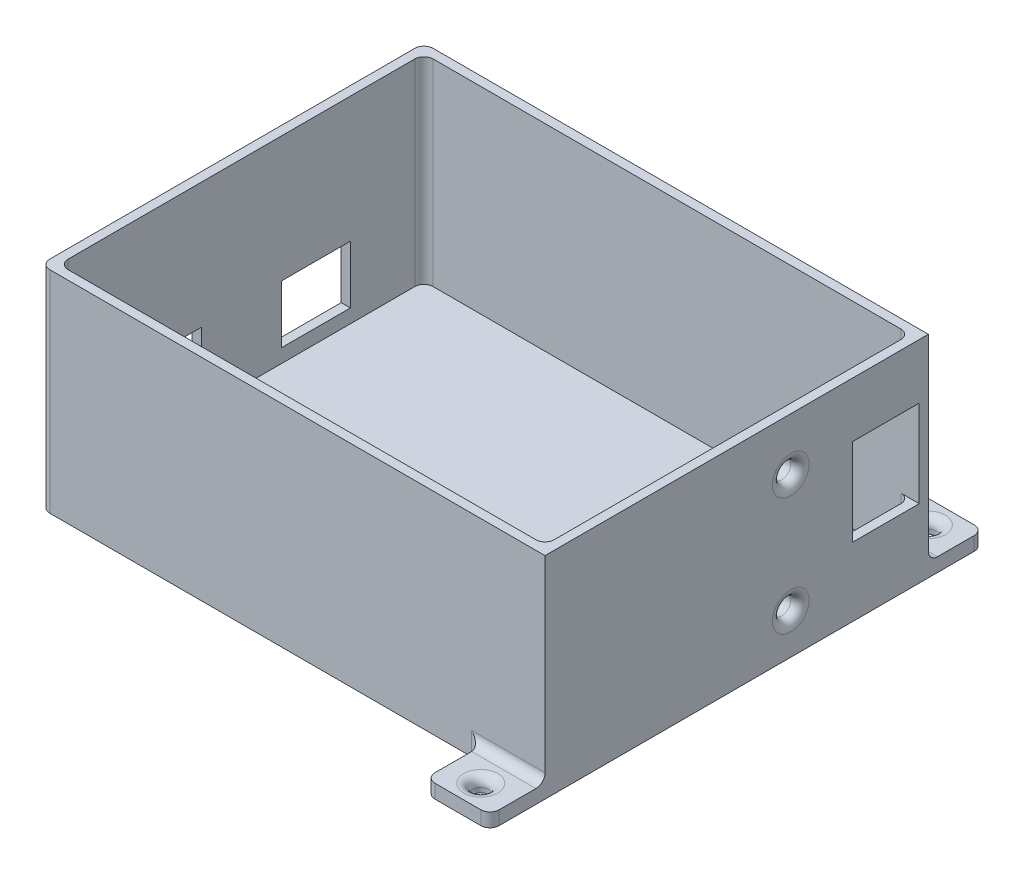
SolidWorks part; units mm, degrees
ref_plane "Front Plane" through (0, 0, 0) normal (0, 0, 1) x (1, 0, 0)
ref_plane "Top Plane" through (0, 0, 0) normal (0, 1, 0) x (1, 0, 0)
ref_plane "Right Plane" through (0, 0, 0) normal (1, 0, 0) x (0, 0, -1)
sketch "Sketch2" plane through (0, 0, 0) normal (0, 1, 0) x (1, 0, 0)
  line L1 (-16, 0) -> (-108, 0)
  line L2 (0, 0) -> (0, 83.6)
  line L3 (-16, 83.6) -> (-108, 83.6)
  line L4 (-110, 2) -> (-110, 81.6)
  line L5 (0, 0) -> (-16, 0)
  line L6 (0, 0) -> (0, -10)
  line L7 (-2, -12) -> (-12, -12)
  line L8 (-14, -2) -> (-14, -10)
  line L9 (0, 83.6) -> (-16, 83.6)
  line L10 (0, 83.6) -> (0, 93.6)
  line L11 (-2, 95.6) -> (-12, 95.6)
  line L12 (-14, 85.6) -> (-14, 93.6)
  arc A1 (-12, 95.6) -> (-14, 93.6) centre (-12, 93.6) ccw
  arc A2 (0, 93.6) -> (-2, 95.6) centre (-2, 93.6) ccw
  arc A3 (-16, 83.6) -> (-14, 85.6) centre (-16, 85.6) ccw
  arc A4 (-16, 0) -> (-14, -2) centre (-16, -2) cw
  arc A5 (-14, -10) -> (-12, -12) centre (-12, -10) ccw
  arc A6 (0, -10) -> (-2, -12) centre (-2, -10) cw
  arc A7 (-108, 0) -> (-110, 2) centre (-108, 2) cw
  arc A8 (-110, 81.6) -> (-108, 83.6) centre (-108, 81.6) cw
  dimension "D7" = 2
  dimension "D8" = 2
  dimension "D5" = 2
  dimension "D1" = 2
  dimension "D6" = 2
  dimension "D2" = 95.6
  dimension "D3" = 12
  dimension "D4" = 110
extrude "Boss-Extrude1" add sketch "Sketch2" along normal blind 46 contours A8 L4 A7 L1 L5 L2 L9 L3 region at (-54.9898, 0, -41.8)
extrude "Boss-Extrude2" add sketch "Sketch2<7>" along normal blind 3 contours A3 L9 L10 A2 L11 A1 L12 region at (-7.0382, 0, -89.5144)
sketch "Sketch2<7>" plane through (0, 0, 0) normal (0, 1, 0) x (1, 0, 0) same geometry as "Sketch2"
extrude "Boss-Extrude3" add sketch "Sketch2<8>" along normal blind 3 contours A6 L6 L5 A4 L8 A5 L7 region at (-7.0382, 0, 5.9144)
sketch "Sketch2<8>" plane through (0, 0, 0) normal (0, 1, 0) x (1, 0, 0) same geometry as "Sketch2"
fillet "Fillet1" radius 2 1 edges at (-8, 3, -83.6)
fillet "Fillet2" radius 2 1 edges at (-8, 3, 0)
sketch "Sketch3" plane through (0, 0, 0) normal (0, 1, 0) x (1, 0, 0)
  line L0 (-14, -2) -> (-14, -10) construction
  line L1 (-25.3, 0) -> (25.3, 0) construction
  line L2 (-14, 85.6) -> (-14, 93.6) construction
  line L4 (0, 83.6) -> (-108, 83.6) construction
  circle A0 centre (-7, -7) radius 1.7
  circle A1 centre (-7, 90.6) radius 1.7
  dimension "D1" = 7
  dimension "D3" = 7
  dimension "D2" = 7
  dimension "D4" = 7
extrude "Cut-Extrude5" cut sketch "Sketch3" along normal up to next
fillet "Fillet3" radius 2 2 edges at (-7, 3, 8.7) (-7, 3, -88.9)
sketch "Sketch4" plane through (0, 46, 0) normal (0, 1, 0) x (1, 0, 0)
  line L0 (0, 83.6) -> (-108, 83.6) construction
  line L1 (-106, 81.6) -> (-4, 81.6)
  line L2 (-108, 79.6) -> (-108, 4)
  line L3 (-106, 2) -> (-4, 2)
  line L4 (-2, 79.6) -> (-2, 4)
  line L5 (-110, 2) -> (-110, 81.6) construction
  line L6 (0, -25.3) -> (0, 25.3) construction
  line L7 (-25.3, 0) -> (25.3, 0) construction
  arc A0 (-2, 79.6) -> (-4, 81.6) centre (-4, 79.6) ccw
  arc A1 (-2, 4) -> (-4, 2) centre (-4, 4) cw
  arc A2 (-106, 2) -> (-108, 4) centre (-106, 4) cw
  arc A3 (-106, 81.6) -> (-108, 79.6) centre (-106, 79.6) ccw
  dimension "D5" = 2
  dimension "D1" = 2
  dimension "D2" = 2
  dimension "D3" = 2
  dimension "D4" = 2
extrude "Cut-Extrude6" cut sketch "Sketch4" against normal blind 43 contours L2 A2 L3 A1 L4 A0 L1 A3
sketch "Sketch5" plane through (0, 0, 0) normal (0, 1, 0) x (1, 0, 0)
  line L0 (-2, 63) -> (-6.6, 63)
  line L1 (-2, 79.6) -> (-2, 4) construction
  line L2 (-6.6, 63) -> (-6.6, 43.6)
  line L3 (-6.6, 43.6) -> (-2, 43.6)
  line L4 (-2, 79.6) -> (-2, 4) construction
  line L5 (0, 83.6) -> (-16, 83.6) construction
  line L6 (-25.3, 0) -> (25.3, 0) construction
  line L7 (0, -25.3) -> (0, 25.3) construction
  line L8 (-2, 63) -> (-2, 43.6)
  dimension "D1" = 40
  dimension "D2" = 63
  dimension "D3" = 6.6
extrude "Boss-Extrude4" add sketch "Sketch5" along normal blind 46 contours L8 L3 L2 L0
sketch "Sketch6" plane through (0, 46, 0) normal (0, 1, 0) x (1, 0, 0)
  line L0 (-2, 63) -> (-2, 43.6)
  line L1 (-2, 63) -> (-6.6, 63)
  line L2 (-6.6, 63) -> (-6.6, 43.6)
  line L3 (-6.6, 43.6) -> (-2, 43.6)
extrude "Cut-Extrude8" cut sketch "Sketch6" against normal blind 5
sketch "Sketch7" plane through (0, 41, 0) normal (0, 1, 0) x (1, 0, 0)
  line L0 (-2, 63) -> (-2, 59.4)
  line L1 (-2, 79.6) -> (-2, 4) construction
  line L2 (-2, 59.4) -> (-6.6, 59.4)
  line L3 (-6.6, 43.6) -> (-6.6, 63) construction
  line L4 (-2, 43.6) -> (-2, 47.2)
  line L5 (-2, 43.6) -> (-2, 63) construction
  line L6 (-2, 47.2) -> (-6.6, 47.2)
  line L7 (-6.6, 63) -> (-6.6, 43.6) construction
  line L8 (-5, 59.4) -> (-5, 47.2)
  line L9 (0, -25.3) -> (0, 25.3) construction
  line L10 (-6.6, 59.4) -> (-6.6, 47.2)
  line L11 (-5, 47.2) -> (-6.6, 47.2)
  line L12 (-6.6, 59.4) -> (-5, 59.4)
  line M2 (-6.6, 63) -> (-6.6, 43.6)
  dimension "D1" = 3.6
  dimension "D2" = 3.6
  dimension "D3" = 5
extrude "Cut-Extrude10" cut sketch "Sketch7" against normal up to vertex (38 mm away) contours L8 L2 L6 M2 region at (-5.8, 41, -53.3) up to point (-6.6, 3, -43.6)
chamfer "Chamfer1" distance 5 angle 45 1 edges at (-6.6, 41, -61.2)
sketch "Sketch8" plane through (0, 0, 0) normal (1, 0, 0) x (0, 0, -1)
  line L0 (59.18, 0) -> (-59.18, 0) construction
  line L1 (83.6, 46) -> (83.6, 5) construction
  circle A0 centre (53.6, 8.8) radius 2
  circle A1 centre (53.6, 34.5) radius 2
  dimension "D2" = 34.5
  dimension "D3" = 30
  dimension "D1" = 8.8
  dimension "D4" = 30
extrude "Cut-Extrude11" cut sketch "Sketch8" against normal blind 34.5
fillet "Fillet4" radius 2 2 edges at (0, 8.8, -55.6) (0, 34.5, -55.6)
sketch "Sketch12" plane through (-110, 0, 0) normal (-1, 0, 0) x (0, 0, 1)
  line L0 (-41.8, 46) -> (-41.8, 0)
  line L1 (-2, 46) -> (-81.6, 46) construction
  line L2 (-2, 0) -> (-81.6, 0) construction
  line L3 (-83.6, 46) -> (-83.6, 0) construction
  line L5 (-65.55, 18.6) -> (-50.55, 18.6)
  line L6 (-65.55, 18.6) -> (-65.55, 6)
  line L7 (-65.55, 6) -> (-50.55, 6)
  line L8 (-50.55, 18.6) -> (-50.55, 6)
  line L9 (-33.05, 18.6) -> (-22.55, 18.6)
  line L10 (-33.05, 18.6) -> (-33.05, 6)
  line L11 (-33.05, 6) -> (-22.55, 6)
  line L12 (-22.55, 18.6) -> (-22.55, 6)
  dimension "D1" = 41.8
  dimension "D2" = 15
  dimension "D3" = 10.5
  dimension "D4" = 17.5
  dimension "D5" = 8.75
  dimension "D6" = 6
  dimension "D7" = 6
  dimension "D8" = 12.6
  dimension "D9" = 12.6
extrude "Cut-Extrude13" cut sketch "Sketch12" against normal blind 34.5 contours L8 L5 L6 L7 | L12 L9 L10 L11 region at (-110, 12.3, -58.05) region at (-110, 12.3, -27.8)
sketch "Sketch14" plane through (0, 0, 0) normal (1, 0, 0) x (0, 0, -1)
  line L0 (59.18, 0) -> (-59.18, 0) construction
  line L1 (67.1, 34) -> (81.6, 34)
  line L2 (67.1, 34) -> (67.1, 15)
  line L3 (67.1, 15) -> (81.6, 15)
  line L4 (81.6, 34) -> (81.6, 15)
  line L5 (83.6, 46) -> (83.6, 5) construction
  dimension "D1" = 15
  dimension "D2" = 2
  dimension "D3" = 14.5
  dimension "D4" = 19
extrude "Cut-Extrude14" cut sketch "Sketch14" against normal blind 10 contours L2 L1 L4 L3
